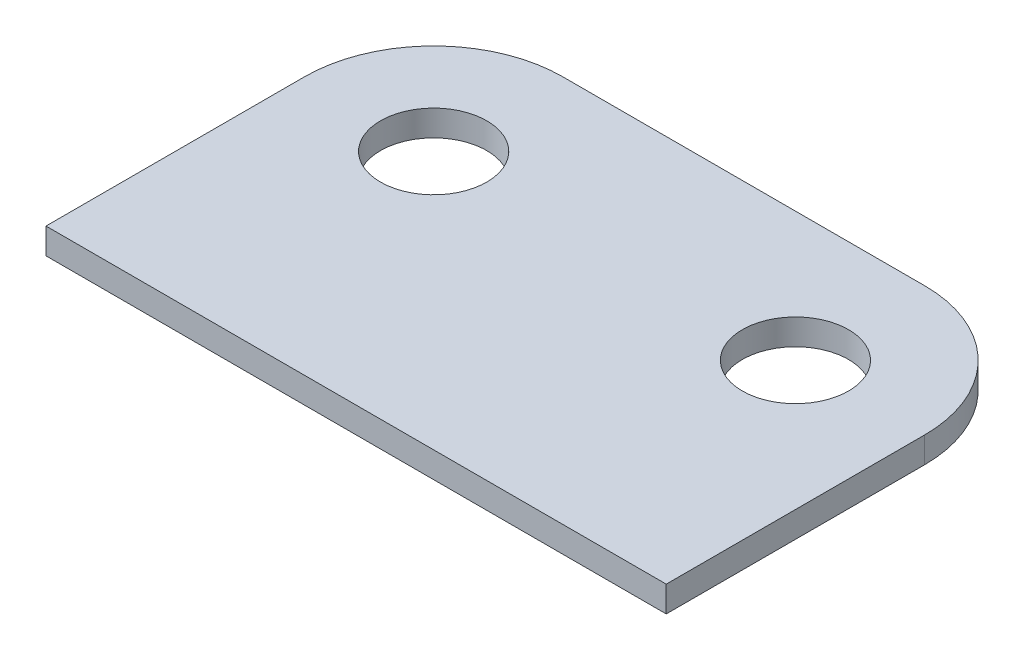
SolidWorks part; units mm, degrees
material "AISI 1020"
ref_plane "Front Plane" through (0, 0, 0) normal (0, 0, 1) x (1, 0, 0)
ref_plane "Top Plane" through (0, 0, 0) normal (0, 1, 0) x (1, 0, 0)
ref_plane "Right Plane" through (0, 0, 0) normal (1, 0, 0) x (0, 0, -1)
sketch "Sketch1" plane through (0, 0, 0) normal (0, 1, 0) x (1, 0, 0)
  line L0 (-19.05, 0) -> (19.05, 0)
  line L1 (19.05, 0) -> (19.05, 15.875)
  line L2 (-19.05, 15.875) -> (-19.05, 0)
  line L3 (-11.1125, 23.8125) -> (11.1125, 23.8125)
  arc A0 (19.05, 15.875) -> (11.1125, 23.8125) centre (11.1125, 15.875) ccw
  arc A2 (-11.1125, 23.8125) -> (-19.05, 15.875) centre (-11.1125, 15.875) ccw
  circle A3 centre (-11.1125, 15.875) radius 3.2639
  circle A4 centre (11.1125, 15.875) radius 3.2639
  point P4 (0, 0)
  dimension "D1" = 6.5278
  dimension "D2" = 38.1
  dimension "D4" = 22.225
  dimension "D3" = 15.875
extrude "Boss-Extrude1" add sketch "Sketch1" along normal blind 1.5875
sketch "Sketch3" plane through (0, 0, -23.8125) normal (0, 0, -1) x (-1, 0, 0)
  line L0 (-11.1125, 1.5875) -> (11.1125, 1.5875) construction
  point P0 (0, 1.5875)
